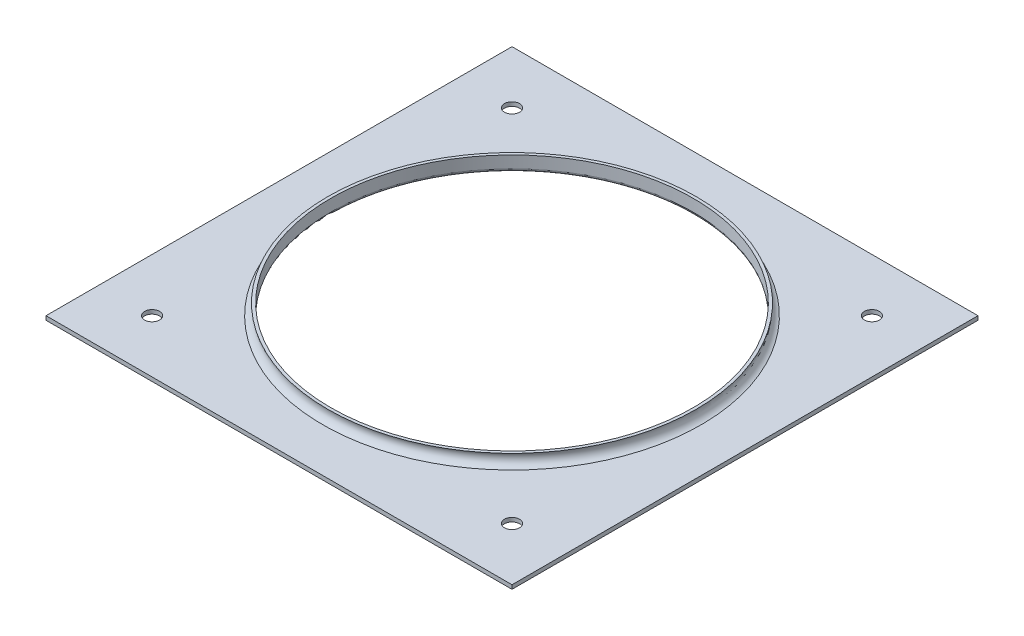
SolidWorks part; units mm, degrees
ref_plane "Alzado" through (0, 0, 0) normal (0, 0, 1) x (1, 0, 0)
ref_plane "Planta" through (0, 0, 0) normal (0, 1, 0) x (1, 0, 0)
ref_plane "Vista lateral" through (0, 0, 0) normal (1, 0, 0) x (0, 0, -1)
sketch "Croquis1" plane through (0, 0, 0) normal (0, 1, 0) x (1, 0, 0)
  line L1 (77.5, -77.5) -> (-77.5, -77.5)
  line L2 (77.5, -77.5) -> (77.5, 77.5)
  line L3 (77.5, 77.5) -> (-77.5, 77.5)
  line L4 (-77.5, -77.5) -> (-77.5, 77.5)
  line L5 (77.5, -77.5) -> (-77.5, 77.5) construction
  line L6 (77.5, 77.5) -> (-77.5, -77.5) construction
  circle A0 centre (0, 0) radius 60.3
  point P0 (0, 0)
  dimension "D3" = 120.6
  dimension "D1" = 155
  dimension "D2" = 155
extrude "Saliente-Extruir1" add sketch "Croquis1" along normal blind 8
sketch "Croquis2" plane through (0, 0, 0) normal (0, 0, 1) x (1, 0, 0)
  line L0 (77.5, 8) -> (77.5, 0) construction
  line L1 (63.0578, 6.4741) -> (73.2214, 6.4741)
  line L3 (62.8889, 1.3294) -> (77.5, 1.3294)
  line L8 (77.5, 1.3294) -> (118.6057, 1.3294)
  line L9 (0, 0) -> (0, 13.4766) construction
  line L11 (73.2214, 6.4741) -> (118.6057, 6.4741)
  line L12 (118.6057, 1.3294) -> (118.6057, 6.4741)
  arc A0 (63.0578, 6.4741) -> (62.8889, 1.3294) centre (63.7046, 3.8778) ccw
revolve "Cortar-Revolución1" cut sketch "Croquis2" angle 360 about L9
sketch "Croquis3" plane through (0, 8, 0) normal (0, 1, 0) x (1, 0, 0)
  line L4 (-77.5, 77.5) -> (-77.5, -77.5)
  line L5 (-77.5, -77.5) -> (77.5, -77.5)
  line L6 (77.5, -77.5) -> (77.5, 77.5)
  line L7 (77.5, 77.5) -> (-77.5, 77.5)
  line L9 (-77.5, -77.5) -> (77.5, -77.5)
  line L11 (77.5, 77.5) -> (-77.5, 77.5)
  circle A0 centre (70, 70) radius 3.5
  circle A1 centre (-70, 70) radius 3.5
  circle A2 centre (-70, -70) radius 3.5
  circle A3 centre (70, -70) radius 3.5
  dimension "D3" = 7
  dimension "D4" = 7
  dimension "D5" = 7
  dimension "D6" = 7
  dimension "D7" = 70
  dimension "D8" = 140
  dimension "D2" = 140
  dimension "D9" = 140
  dimension "D10" = 70
  dimension "D1" = 0
extrude "Cortar-Extruir4" cut sketch "Croquis3" against normal up to next contours A0 | A1 | A2 | A3
fillet "Redondeo1" radius 1 2 edges at (0, 0, 60.3) (0, 8, 60.3)
sketch "Croquis4" plane through (0, 0, 0) normal (0, -1, 0) x (1, 0, 0)
  line L5 (59.8566, -59.8566) -> (-59.8566, 59.8566) construction
  line L6 (59.8566, 59.8566) -> (-59.8566, -59.8566) construction
  line L8 (0, 28.0777) -> (0, -41.9914) construction
  point P0 (0, 0)
  point P6 (0, 0)
  point P7 (0, 0)
  point P11 (59.8566, -59.8566)
  point P12 (-59.8566, -59.8566)
  point P13 (-59.8566, 59.8566)
  point P14 (59.8566, 59.8566)
  dimension "D3" = 45
  dimension "D1" = 169.3
  dimension "D2" = 45
ref_plane "Plano1" through (0, 5, 0) normal (0, 1, 0) x (1, 0, 0)
sketch "Croquis5" plane through (0, 5, 0) normal (0, 1, 0) x (1, 0, 0)
  line L1 (80.693, -79.3953) -> (-80.693, -79.3953)
  line L2 (80.693, -79.3953) -> (80.693, 79.3953)
  line L3 (80.693, 79.3953) -> (-80.693, 79.3953)
  line L4 (-80.693, -79.3953) -> (-80.693, 79.3953)
  line L5 (80.693, -79.3953) -> (-80.693, 79.3953) construction
  line L6 (80.693, 79.3953) -> (-80.693, -79.3953) construction
  point P0 (0, 0)
extrude "Cortar-Extruir6" cut sketch "Croquis5" along normal blind 30
hole_wizard "Ø5.0 (5) Diameter Hole1" positions "Sketch1" profile "Sketch2" hole size "Ø5.0" standard "ANSI Metric" end condition through all
sketch "Sketch1" plane through (0, 0, 0) normal (0, -1, 0) x (-1, 0, 0)
  point P0 (-59.8566, -59.8566)
  point P3 (-59.8566, 59.8566)
  point P6 (59.8566, 59.8566)
  point P9 (59.8566, -59.8566)
sketch "Sketch2" plane through (59.8566, 0, 59.8566) normal (1, 0, 0) x (0, 0, -1)
  line L0 (0, 0) -> (0, 5)
  line L1 (0, 5) -> (2.5, 5)
  line L2 (2.5, 5) -> (2.5, 0)
  line L5 (2.5, 0) -> (0, 0)
  line L11 (0, -6.35) -> (0, 107.95) construction
  dimension "Thru Hole Dia." = 5
  dimension "Thru Hole Depth" = 5
equation "\"D2@Croquis1\"=\"D1@Croquis1\""
